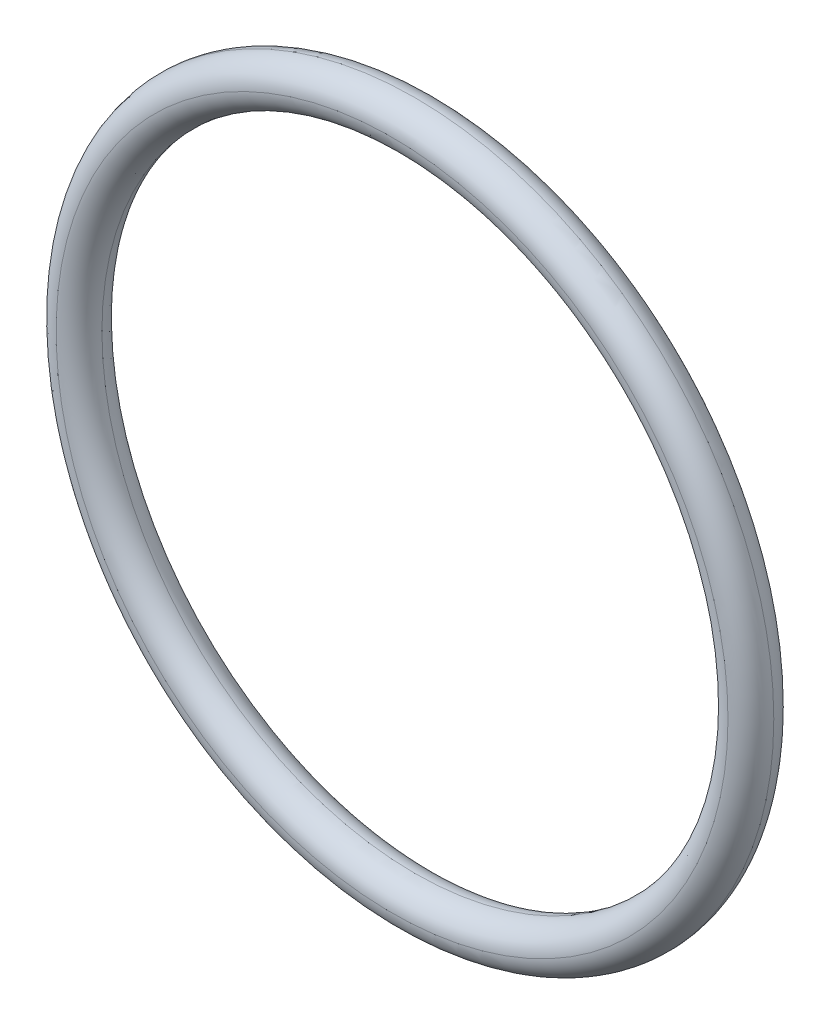
SolidWorks part; units mm, degrees
material "Rubber"
ref_plane "Front Plane" through (0, 0, 0) normal (0, 0, 1) x (1, 0, 0)
ref_plane "Top Plane" through (0, 0, 0) normal (0, 1, 0) x (1, 0, 0)
ref_plane "Right Plane" through (0, 0, 0) normal (1, 0, 0) x (0, 0, -1)
other "Configuration Table"
sketch "Sketch1" plane through (0, 0, 0) normal (0, 0, 1) x (1, 0, 0)
  circle A0 centre (0, 0) radius 7.8613
  circle A1 centre (0, 0) radius 6.858
  dimension "D1" = 15.7226
  dimension "D2" = 13.716
extrude "Boss-Extrude1" add sketch "Sketch1" against normal blind 2.0066
sketch "Sketch2" plane through (0, 0, 0) normal (1, 0, 0) x (0, 0, -1)
  line L0 (0, -7.8613) -> (2.0066, -7.8613) construction
  line L1 (2.0066, 7.8613) -> (1.0033, 7.8613)
  line L2 (2.0066, 7.8613) -> (2.0066, -7.8613)
  line L3 (2.0066, -7.8613) -> (1.0033, -7.8613)
  line L4 (1.0033, 7.8613) -> (1.0033, -7.8613)
  line L7 (0, 7.8613) -> (0, -7.8613) construction
  dimension "D1" = 1.0033
extrude "Cut-Extrude1" cut sketch "Sketch2" along normal through all both and the other way through all
fillet "Fillet1" radius 0.5016 3 edges at (7.8613, 0, 0) (0, 6.858, -1.0033) (6.858, 0, 0)
fillet "Fillet2" radius 0.5016 1 edges at (0, 7.8613, -1.0033)
